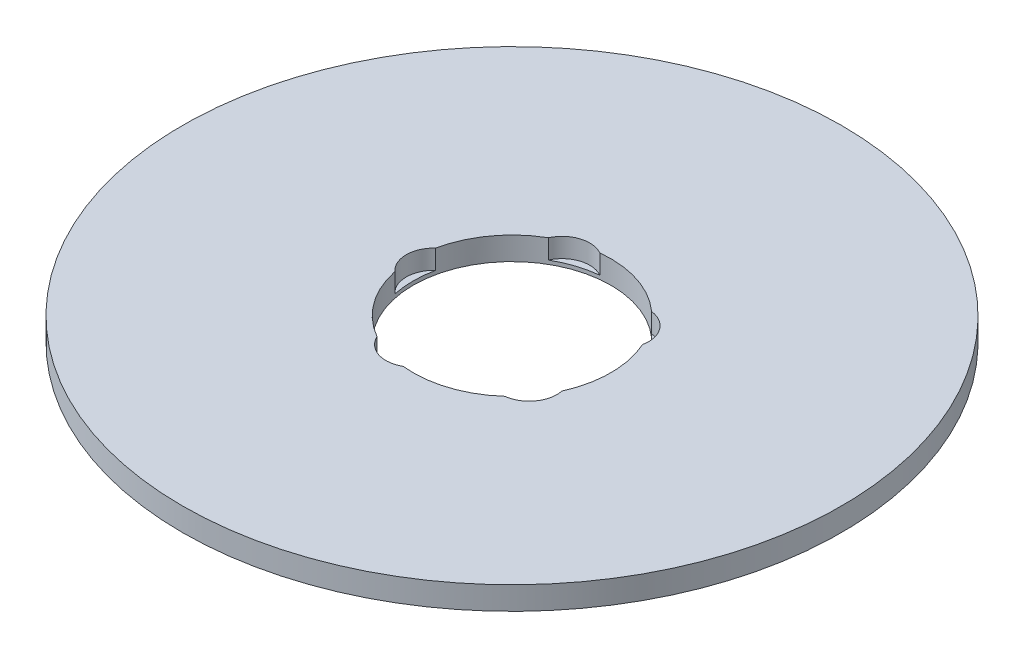
SolidWorks part; units mm, degrees
ref_plane "Front Plane" through (0, 0, 0) normal (0, 0, 1) x (1, 0, 0)
ref_plane "Top Plane" through (0, 0, 0) normal (0, 1, 0) x (1, 0, 0)
ref_plane "Right Plane" through (0, 0, 0) normal (1, 0, 0) x (0, 0, -1)
sketch "Sketch1" plane through (0, 0, 0) normal (0, 1, 0) x (1, 0, 0)
  circle A0 centre (0, 0) radius 100
  dimension "FLANGE_OD" = 200
extrude "Boss-Extrude1" add sketch "Sketch1" along normal blind 7
sketch "Sketch2" plane through (0, 0, 0) normal (0, 1, 0) x (1, 0, 0)
  circle A0 centre (0, 0) radius 30
  dimension "BORE_D" = 60
extrude "Cut-Extrude1" cut sketch "Sketch2" along normal through all
sketch "Sketch3" plane through (0, 7, 0) normal (0, 1, 0) x (1, 0, 0)
  circle A0 centre (0, 0) radius 23.657 construction
  circle A1 centre (-23.657, 0) radius 8.4161
  dimension "BOLT_D" = 16.8321
  dimension "BOLT_PCD" = 47.3139
extrude "Cut-Extrude2" cut sketch "Sketch3" against normal blind 5.8639
pattern_circular "CirPattern1" count 5 over 360 about axis through (0, 0, 0) along (0, 1, 0) of "Cut-Extrude2"
